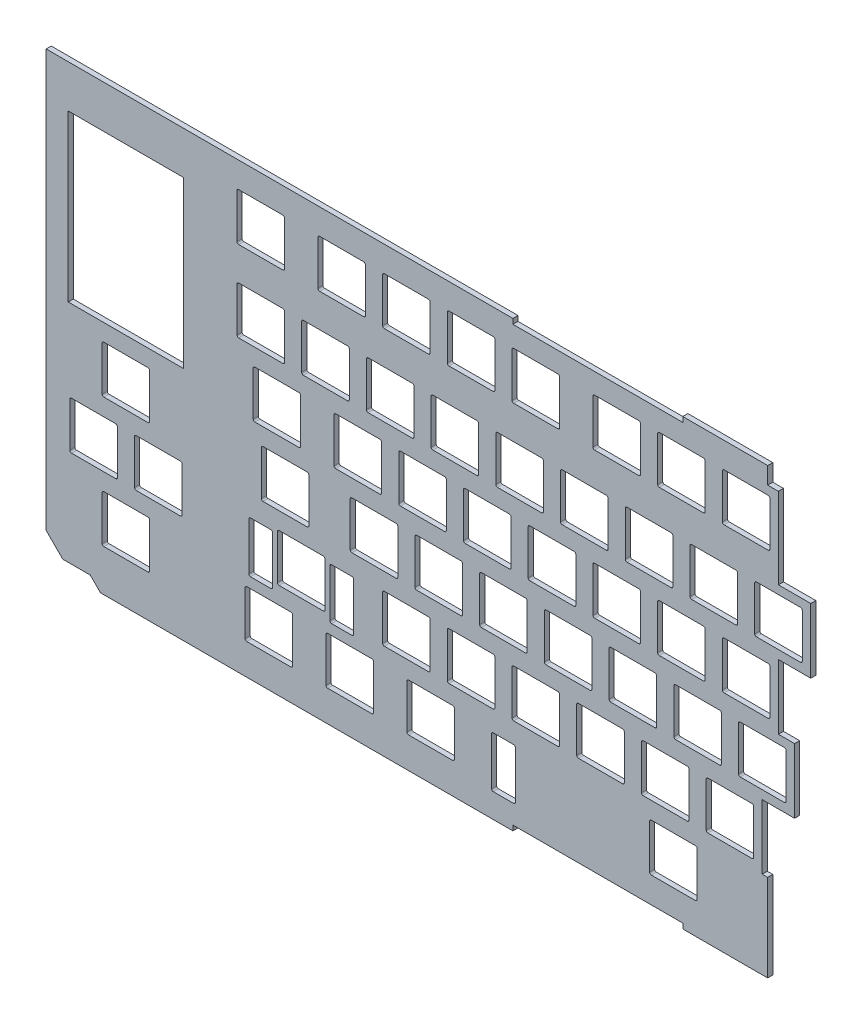
SolidWorks part; units mm, degrees
ref_plane "Přední rovina" through (0, 0, 0) normal (0, 0, 1) x (1, 0, 0)
ref_plane "Horní rovina" through (0, 0, 0) normal (0, 1, 0) x (1, 0, 0)
ref_plane "Pravá rovina" through (0, 0, 0) normal (1, 0, 0) x (0, 0, -1)
sketch "Model" plane through (0, 0, 0) normal (0, 0, 1) x (1, 0, 0)
  line L0 (53.8256, -2.525) -> (66.8256, -2.525)
  line L1 (53.8256, -16.525) -> (66.8256, -16.525)
  line L2 (53.3256, -3.025) -> (53.3256, -16.025)
  line L3 (67.3256, -3.025) -> (67.3256, -16.025)
  line L4 (77.6381, -2.525) -> (90.6381, -2.525)
  line L5 (77.6381, -16.525) -> (90.6381, -16.525)
  line L6 (77.1381, -3.025) -> (77.1381, -16.025)
  line L7 (91.1381, -3.025) -> (91.1381, -16.025)
  line L8 (96.6881, -2.525) -> (109.6881, -2.525)
  line L9 (96.6881, -16.525) -> (109.6881, -16.525)
  line L10 (96.1881, -3.025) -> (96.1881, -16.025)
  line L11 (110.1881, -3.025) -> (110.1881, -16.025)
  line L12 (115.7381, -2.525) -> (128.7381, -2.525)
  line L13 (115.7381, -16.525) -> (128.7381, -16.525)
  line L14 (115.2381, -3.025) -> (115.2381, -16.025)
  line L15 (129.2381, -3.025) -> (129.2381, -16.025)
  line L16 (134.7881, -2.525) -> (147.7881, -2.525)
  line L17 (134.7881, -16.525) -> (147.7881, -16.525)
  line L18 (134.2881, -3.025) -> (134.2881, -16.025)
  line L19 (148.2881, -3.025) -> (148.2881, -16.025)
  line L20 (158.6006, -2.525) -> (171.6006, -2.525)
  line L21 (158.6006, -16.525) -> (171.6006, -16.525)
  line L22 (158.1006, -3.025) -> (158.1006, -16.025)
  line L23 (172.1006, -3.025) -> (172.1006, -16.025)
  line L24 (177.6506, -2.525) -> (190.6506, -2.525)
  line L25 (177.6506, -16.525) -> (190.6506, -16.525)
  line L26 (177.1506, -3.025) -> (177.1506, -16.025)
  line L27 (191.1506, -3.025) -> (191.1506, -16.025)
  line L28 (196.7006, -2.525) -> (209.7006, -2.525)
  line L29 (196.7006, -16.525) -> (209.7006, -16.525)
  line L30 (196.2006, -3.025) -> (196.2006, -16.025)
  line L31 (210.2006, -3.025) -> (210.2006, -16.025)
  line L32 (215.7506, -2.525) -> (228.7506, -2.525)
  line L33 (215.7506, -16.525) -> (228.7506, -16.525)
  line L34 (215.2506, -3.025) -> (215.2506, -16.025)
  line L35 (229.2506, -3.025) -> (229.2506, -16.025)
  line L36 (239.5631, -2.525) -> (252.5631, -2.525)
  line L37 (239.5631, -16.525) -> (252.5631, -16.525)
  line L38 (239.0631, -3.025) -> (239.0631, -16.025)
  line L39 (253.0631, -3.025) -> (253.0631, -16.025)
  line L40 (258.6131, -2.525) -> (271.6131, -2.525)
  line L41 (258.6131, -16.525) -> (271.6131, -16.525)
  line L42 (258.1131, -3.025) -> (258.1131, -16.025)
  line L43 (272.1131, -3.025) -> (272.1131, -16.025)
  line L44 (277.6631, -2.525) -> (290.6631, -2.525)
  line L45 (277.6631, -16.525) -> (290.6631, -16.525)
  line L46 (277.1631, -3.025) -> (277.1631, -16.025)
  line L47 (291.1631, -3.025) -> (291.1631, -16.025)
  line L48 (296.7131, -2.525) -> (309.7131, -2.525)
  line L49 (296.7131, -16.525) -> (309.7131, -16.525)
  line L50 (296.2131, -3.025) -> (296.2131, -16.025)
  line L51 (310.2131, -3.025) -> (310.2131, -16.025)
  line L52 (320.5256, -2.525) -> (333.5256, -2.525)
  line L53 (320.5256, -16.525) -> (333.5256, -16.525)
  line L54 (320.0256, -3.025) -> (320.0256, -16.025)
  line L55 (334.0256, -3.025) -> (334.0256, -16.025)
  line L56 (344.3381, -2.525) -> (357.3381, -2.525)
  line L57 (344.3381, -16.525) -> (357.3381, -16.525)
  line L58 (343.8381, -3.025) -> (343.8381, -16.025)
  line L59 (357.8381, -3.025) -> (357.8381, -16.025)
  line L60 (363.3881, -2.525) -> (376.3881, -2.525)
  line L61 (363.3881, -16.525) -> (376.3881, -16.525)
  line L62 (362.8881, -3.025) -> (362.8881, -16.025)
  line L63 (376.8881, -3.025) -> (376.8881, -16.025)
  line L64 (382.4381, -2.525) -> (395.4381, -2.525)
  line L65 (382.4381, -16.525) -> (395.4381, -16.525)
  line L66 (381.9381, -3.025) -> (381.9381, -16.025)
  line L67 (395.9381, -3.025) -> (395.9381, -16.025)
  line L68 (401.4881, -2.525) -> (414.4881, -2.525)
  line L69 (401.4881, -16.525) -> (414.4881, -16.525)
  line L70 (400.9881, -3.025) -> (400.9881, -16.025)
  line L71 (414.9881, -3.025) -> (414.9881, -16.025)
  line L72 (53.8256, -26.3375) -> (66.8256, -26.3375)
  line L73 (53.8256, -40.3375) -> (66.8256, -40.3375)
  line L74 (53.3256, -26.8375) -> (53.3256, -39.8375)
  line L75 (67.3256, -26.8375) -> (67.3256, -39.8375)
  line L76 (72.8756, -26.3375) -> (85.8756, -26.3375)
  line L77 (72.8756, -40.3375) -> (85.8756, -40.3375)
  line L78 (72.3756, -26.8375) -> (72.3756, -39.8375)
  line L79 (86.3756, -26.8375) -> (86.3756, -39.8375)
  line L80 (91.9256, -26.3375) -> (104.9256, -26.3375)
  line L81 (91.9256, -40.3375) -> (104.9256, -40.3375)
  line L82 (91.4256, -26.8375) -> (91.4256, -39.8375)
  line L83 (105.4256, -26.8375) -> (105.4256, -39.8375)
  line L84 (110.9756, -26.3375) -> (123.9756, -26.3375)
  line L85 (110.9756, -40.3375) -> (123.9756, -40.3375)
  line L86 (110.4756, -26.8375) -> (110.4756, -39.8375)
  line L87 (124.4756, -26.8375) -> (124.4756, -39.8375)
  line L88 (130.0256, -26.3375) -> (143.0256, -26.3375)
  line L89 (130.0256, -40.3375) -> (143.0256, -40.3375)
  line L90 (129.5256, -26.8375) -> (129.5256, -39.8375)
  line L91 (143.5256, -26.8375) -> (143.5256, -39.8375)
  line L92 (149.0756, -26.3375) -> (162.0756, -26.3375)
  line L93 (149.0756, -40.3375) -> (162.0756, -40.3375)
  line L94 (148.5756, -26.8375) -> (148.5756, -39.8375)
  line L95 (162.5756, -26.8375) -> (162.5756, -39.8375)
  line L96 (168.1256, -26.3375) -> (181.1256, -26.3375)
  line L97 (168.1256, -40.3375) -> (181.1256, -40.3375)
  line L98 (167.6256, -26.8375) -> (167.6256, -39.8375)
  line L99 (181.6256, -26.8375) -> (181.6256, -39.8375)
  line L100 (187.1756, -26.3375) -> (200.1756, -26.3375)
  line L101 (187.1756, -40.3375) -> (200.1756, -40.3375)
  line L102 (186.6756, -26.8375) -> (186.6756, -39.8375)
  line L103 (200.6756, -26.8375) -> (200.6756, -39.8375)
  line L104 (206.2256, -26.3375) -> (219.2256, -26.3375)
  line L105 (206.2256, -40.3375) -> (219.2256, -40.3375)
  line L106 (205.7256, -26.8375) -> (205.7256, -39.8375)
  line L107 (219.7256, -26.8375) -> (219.7256, -39.8375)
  line L108 (225.2756, -26.3375) -> (238.2756, -26.3375)
  line L109 (225.2756, -40.3375) -> (238.2756, -40.3375)
  line L110 (224.7756, -26.8375) -> (224.7756, -39.8375)
  line L111 (238.7756, -26.8375) -> (238.7756, -39.8375)
  line L112 (244.3256, -26.3375) -> (257.3256, -26.3375)
  line L113 (244.3256, -40.3375) -> (257.3256, -40.3375)
  line L114 (243.8256, -26.8375) -> (243.8256, -39.8375)
  line L115 (257.8256, -26.8375) -> (257.8256, -39.8375)
  line L116 (263.3756, -26.3375) -> (276.3756, -26.3375)
  line L117 (263.3756, -40.3375) -> (276.3756, -40.3375)
  line L118 (262.8756, -26.8375) -> (262.8756, -39.8375)
  line L119 (276.8756, -26.8375) -> (276.8756, -39.8375)
  line L120 (282.4256, -26.3375) -> (295.4256, -26.3375)
  line L121 (282.4256, -40.3375) -> (295.4256, -40.3375)
  line L122 (281.9256, -26.8375) -> (281.9256, -39.8375)
  line L123 (295.9256, -26.8375) -> (295.9256, -39.8375)
  line L124 (311.0006, -26.3375) -> (324.0006, -26.3375)
  line L125 (311.0006, -40.3375) -> (324.0006, -40.3375)
  line L126 (310.5006, -26.8375) -> (310.5006, -39.8375)
  line L127 (324.5006, -26.8375) -> (324.5006, -39.8375)
  line L128 (302.5626, -27.3375) -> (308.5626, -27.3375)
  line L129 (302.5626, -42.3375) -> (308.5626, -42.3375)
  line L130 (302.0626, -27.8375) -> (302.0626, -41.8375)
  line L131 (309.0626, -27.8375) -> (309.0626, -41.8375)
  line L132 (326.4386, -27.3375) -> (332.4386, -27.3375)
  line L133 (326.4386, -42.3375) -> (332.4386, -42.3375)
  line L134 (325.9386, -27.8375) -> (325.9386, -41.8375)
  line L135 (332.9386, -27.8375) -> (332.9386, -41.8375)
  line L136 (342.7513, -26.3375) -> (355.7513, -26.3375)
  line L137 (342.7513, -40.3375) -> (355.7513, -40.3375)
  line L138 (342.2513, -26.8375) -> (342.2513, -39.8375)
  line L139 (356.2513, -26.8375) -> (356.2513, -39.8375)
  line L140 (361.8013, -26.3375) -> (374.8013, -26.3375)
  line L141 (361.8013, -40.3375) -> (374.8013, -40.3375)
  line L142 (361.3013, -26.8375) -> (361.3013, -39.8375)
  line L143 (375.3013, -26.8375) -> (375.3013, -39.8375)
  line L144 (380.8513, -26.3375) -> (393.8513, -26.3375)
  line L145 (380.8513, -40.3375) -> (393.8513, -40.3375)
  line L146 (380.3513, -26.8375) -> (380.3513, -39.8375)
  line L147 (394.3513, -26.8375) -> (394.3513, -39.8375)
  line L148 (399.9013, -26.3375) -> (412.9013, -26.3375)
  line L149 (399.9013, -40.3375) -> (412.9013, -40.3375)
  line L150 (399.4013, -26.8375) -> (399.4013, -39.8375)
  line L151 (413.4013, -26.8375) -> (413.4013, -39.8375)
  line L152 (58.5881, -45.3875) -> (71.5881, -45.3875)
  line L153 (58.5881, -59.3875) -> (71.5881, -59.3875)
  line L154 (58.0881, -45.8875) -> (58.0881, -58.8875)
  line L155 (72.0881, -45.8875) -> (72.0881, -58.8875)
  line L156 (82.4006, -45.3875) -> (95.4006, -45.3875)
  line L157 (82.4006, -59.3875) -> (95.4006, -59.3875)
  line L158 (81.9006, -45.8875) -> (81.9006, -58.8875)
  line L159 (95.9006, -45.8875) -> (95.9006, -58.8875)
  line L160 (101.4506, -45.3875) -> (114.4506, -45.3875)
  line L161 (101.4506, -59.3875) -> (114.4506, -59.3875)
  line L162 (100.9506, -45.8875) -> (100.9506, -58.8875)
  line L163 (114.9506, -45.8875) -> (114.9506, -58.8875)
  line L164 (120.5006, -45.3875) -> (133.5006, -45.3875)
  line L165 (120.5006, -59.3875) -> (133.5006, -59.3875)
  line L166 (120.0006, -45.8875) -> (120.0006, -58.8875)
  line L167 (134.0006, -45.8875) -> (134.0006, -58.8875)
  line L168 (139.5506, -45.3875) -> (152.5506, -45.3875)
  line L169 (139.5506, -59.3875) -> (152.5506, -59.3875)
  line L170 (139.0506, -45.8875) -> (139.0506, -58.8875)
  line L171 (153.0506, -45.8875) -> (153.0506, -58.8875)
  line L172 (158.6006, -45.3875) -> (171.6006, -45.3875)
  line L173 (158.6006, -59.3875) -> (171.6006, -59.3875)
  line L174 (158.1006, -45.8875) -> (158.1006, -58.8875)
  line L175 (172.1006, -45.8875) -> (172.1006, -58.8875)
  line L176 (177.6506, -45.3875) -> (190.6506, -45.3875)
  line L177 (177.6506, -59.3875) -> (190.6506, -59.3875)
  line L178 (177.1506, -45.8875) -> (177.1506, -58.8875)
  line L179 (191.1506, -45.8875) -> (191.1506, -58.8875)
  line L180 (196.7006, -45.3875) -> (209.7006, -45.3875)
  line L181 (196.7006, -59.3875) -> (209.7006, -59.3875)
  line L182 (196.2006, -45.8875) -> (196.2006, -58.8875)
  line L183 (210.2006, -45.8875) -> (210.2006, -58.8875)
  line L184 (215.7506, -45.3875) -> (228.7506, -45.3875)
  line L185 (215.7506, -59.3875) -> (228.7506, -59.3875)
  line L186 (215.2506, -45.8875) -> (215.2506, -58.8875)
  line L187 (229.2506, -45.8875) -> (229.2506, -58.8875)
  line L188 (234.8006, -45.3875) -> (247.8006, -45.3875)
  line L189 (234.8006, -59.3875) -> (247.8006, -59.3875)
  line L190 (234.3006, -45.8875) -> (234.3006, -58.8875)
  line L191 (248.3006, -45.8875) -> (248.3006, -58.8875)
  line L192 (253.8506, -45.3875) -> (266.8506, -45.3875)
  line L193 (253.8506, -59.3875) -> (266.8506, -59.3875)
  line L194 (253.3506, -45.8875) -> (253.3506, -58.8875)
  line L195 (267.3506, -45.8875) -> (267.3506, -58.8875)
  line L196 (272.9006, -45.3875) -> (285.9006, -45.3875)
  line L197 (272.9006, -59.3875) -> (285.9006, -59.3875)
  line L198 (272.4006, -45.8875) -> (272.4006, -58.8875)
  line L199 (286.4006, -45.8875) -> (286.4006, -58.8875)
  line L200 (291.9506, -45.3875) -> (304.9506, -45.3875)
  line L201 (291.9506, -59.3875) -> (304.9506, -59.3875)
  line L202 (291.4506, -45.8875) -> (291.4506, -58.8875)
  line L203 (305.4506, -45.8875) -> (305.4506, -58.8875)
  line L204 (315.7631, -45.3875) -> (328.7631, -45.3875)
  line L205 (315.7631, -59.3875) -> (328.7631, -59.3875)
  line L206 (315.2631, -45.8875) -> (315.2631, -58.8875)
  line L207 (329.2631, -45.8875) -> (329.2631, -58.8875)
  line L208 (342.7513, -45.3875) -> (355.7513, -45.3875)
  line L209 (342.7513, -59.3875) -> (355.7513, -59.3875)
  line L210 (342.2513, -45.8875) -> (342.2513, -58.8875)
  line L211 (356.2513, -45.8875) -> (356.2513, -58.8875)
  line L212 (361.8013, -45.3875) -> (374.8013, -45.3875)
  line L213 (361.8013, -59.3875) -> (374.8013, -59.3875)
  line L214 (361.3013, -45.8875) -> (361.3013, -58.8875)
  line L215 (375.3013, -45.8875) -> (375.3013, -58.8875)
  line L216 (380.8513, -45.3875) -> (393.8513, -45.3875)
  line L217 (380.8513, -59.3875) -> (393.8513, -59.3875)
  line L218 (380.3513, -45.8875) -> (380.3513, -58.8875)
  line L219 (394.3513, -45.8875) -> (394.3513, -58.8875)
  line L220 (413.4013, -55.4125) -> (413.4013, -68.4125)
  line L221 (399.4013, -55.4125) -> (399.4013, -68.4125)
  line L222 (412.9013, -54.9125) -> (399.9013, -54.9125)
  line L223 (412.9013, -68.9125) -> (399.9013, -68.9125)
  line L224 (412.4013, -46.9745) -> (412.4013, -52.9745)
  line L225 (397.4013, -46.9745) -> (397.4013, -52.9745)
  line L226 (411.9013, -46.4745) -> (397.9013, -46.4745)
  line L227 (411.9013, -53.4745) -> (397.9013, -53.4745)
  line L228 (412.4013, -70.8505) -> (412.4013, -76.8505)
  line L229 (397.4013, -70.8505) -> (397.4013, -76.8505)
  line L230 (411.9013, -70.3505) -> (397.9013, -70.3505)
  line L231 (411.9013, -77.3505) -> (397.9013, -77.3505)
  line L232 (14.1369, -61.2619) -> (27.1369, -61.2619)
  line L233 (14.1369, -75.2619) -> (27.1369, -75.2619)
  line L234 (13.6369, -61.7619) -> (13.6369, -74.7619)
  line L235 (27.6369, -61.7619) -> (27.6369, -74.7619)
  line L236 (60.9694, -64.4375) -> (73.9694, -64.4375)
  line L237 (60.9694, -78.4375) -> (73.9694, -78.4375)
  line L238 (60.4694, -64.9375) -> (60.4694, -77.9375)
  line L239 (74.4694, -64.9375) -> (74.4694, -77.9375)
  line L240 (87.1631, -64.4375) -> (100.1631, -64.4375)
  line L241 (87.1631, -78.4375) -> (100.1631, -78.4375)
  line L242 (86.6631, -64.9375) -> (86.6631, -77.9375)
  line L243 (100.6631, -64.9375) -> (100.6631, -77.9375)
  line L244 (106.2131, -64.4375) -> (119.2131, -64.4375)
  line L245 (106.2131, -78.4375) -> (119.2131, -78.4375)
  line L246 (105.7131, -64.9375) -> (105.7131, -77.9375)
  line L247 (119.7131, -64.9375) -> (119.7131, -77.9375)
  line L248 (125.2631, -64.4375) -> (138.2631, -64.4375)
  line L249 (125.2631, -78.4375) -> (138.2631, -78.4375)
  line L250 (124.7631, -64.9375) -> (124.7631, -77.9375)
  line L251 (138.7631, -64.9375) -> (138.7631, -77.9375)
  line L252 (144.3131, -64.4375) -> (157.3131, -64.4375)
  line L253 (144.3131, -78.4375) -> (157.3131, -78.4375)
  line L254 (143.8131, -64.9375) -> (143.8131, -77.9375)
  line L255 (157.8131, -64.9375) -> (157.8131, -77.9375)
  line L256 (163.3631, -64.4375) -> (176.3631, -64.4375)
  line L257 (163.3631, -78.4375) -> (176.3631, -78.4375)
  line L258 (162.8631, -64.9375) -> (162.8631, -77.9375)
  line L259 (176.8631, -64.9375) -> (176.8631, -77.9375)
  line L260 (182.4131, -64.4375) -> (195.4131, -64.4375)
  line L261 (182.4131, -78.4375) -> (195.4131, -78.4375)
  line L262 (181.9131, -64.9375) -> (181.9131, -77.9375)
  line L263 (195.9131, -64.9375) -> (195.9131, -77.9375)
  line L264 (201.4631, -64.4375) -> (214.4631, -64.4375)
  line L265 (201.4631, -78.4375) -> (214.4631, -78.4375)
  line L266 (200.9631, -64.9375) -> (200.9631, -77.9375)
  line L267 (214.9631, -64.9375) -> (214.9631, -77.9375)
  line L268 (220.5131, -64.4375) -> (233.5131, -64.4375)
  line L269 (220.5131, -78.4375) -> (233.5131, -78.4375)
  line L270 (220.0131, -64.9375) -> (220.0131, -77.9375)
  line L271 (234.0131, -64.9375) -> (234.0131, -77.9375)
  line L272 (239.5631, -64.4375) -> (252.5631, -64.4375)
  line L273 (239.5631, -78.4375) -> (252.5631, -78.4375)
  line L274 (239.0631, -64.9375) -> (239.0631, -77.9375)
  line L275 (253.0631, -64.9375) -> (253.0631, -77.9375)
  line L276 (258.6131, -64.4375) -> (271.6131, -64.4375)
  line L277 (258.6131, -78.4375) -> (271.6131, -78.4375)
  line L278 (258.1131, -64.9375) -> (258.1131, -77.9375)
  line L279 (272.1131, -64.9375) -> (272.1131, -77.9375)
  line L280 (277.6631, -64.4375) -> (290.6631, -64.4375)
  line L281 (277.6631, -78.4375) -> (290.6631, -78.4375)
  line L282 (277.1631, -64.9375) -> (277.1631, -77.9375)
  line L283 (291.1631, -64.9375) -> (291.1631, -77.9375)
  line L284 (308.6194, -64.4375) -> (321.6194, -64.4375)
  line L285 (308.6194, -78.4375) -> (321.6194, -78.4375)
  line L286 (308.1194, -64.9375) -> (308.1194, -77.9375)
  line L287 (322.1194, -64.9375) -> (322.1194, -77.9375)
  line L288 (300.1814, -65.4375) -> (306.1814, -65.4375)
  line L289 (300.1814, -80.4375) -> (306.1814, -80.4375)
  line L290 (299.6814, -65.9375) -> (299.6814, -79.9375)
  line L291 (306.6814, -65.9375) -> (306.6814, -79.9375)
  line L292 (324.0574, -65.4375) -> (330.0574, -65.4375)
  line L293 (324.0574, -80.4375) -> (330.0574, -80.4375)
  line L294 (323.5574, -65.9375) -> (323.5574, -79.9375)
  line L295 (330.5574, -65.9375) -> (330.5574, -79.9375)
  line L296 (342.7513, -64.4375) -> (355.7513, -64.4375)
  line L297 (342.7513, -78.4375) -> (355.7513, -78.4375)
  line L298 (342.2513, -64.9375) -> (342.2513, -77.9375)
  line L299 (356.2513, -64.9375) -> (356.2513, -77.9375)
  line L300 (361.8013, -64.4375) -> (374.8013, -64.4375)
  line L301 (361.8013, -78.4375) -> (374.8013, -78.4375)
  line L302 (361.3013, -64.9375) -> (361.3013, -77.9375)
  line L303 (375.3013, -64.9375) -> (375.3013, -77.9375)
  line L304 (380.8513, -64.4375) -> (393.8513, -64.4375)
  line L305 (380.8513, -78.4375) -> (393.8513, -78.4375)
  line L306 (380.3513, -64.9375) -> (380.3513, -77.9375)
  line L307 (394.3513, -64.9375) -> (394.3513, -77.9375)
  line L308 (4.6119, -80.3119) -> (17.6119, -80.3119)
  line L309 (4.6119, -94.3119) -> (17.6119, -94.3119)
  line L310 (4.1119, -80.8119) -> (4.1119, -93.8119)
  line L311 (18.1119, -80.8119) -> (18.1119, -93.8119)
  line L312 (23.6619, -80.3119) -> (36.6619, -80.3119)
  line L313 (23.6619, -94.3119) -> (36.6619, -94.3119)
  line L314 (23.1619, -80.8119) -> (23.1619, -93.8119)
  line L315 (37.1619, -80.8119) -> (37.1619, -93.8119)
  line L316 (65.7319, -83.4875) -> (78.7319, -83.4875)
  line L317 (65.7319, -97.4875) -> (78.7319, -97.4875)
  line L318 (65.2319, -83.9875) -> (65.2319, -96.9875)
  line L319 (79.2319, -83.9875) -> (79.2319, -96.9875)
  line L320 (57.2939, -84.4875) -> (63.2939, -84.4875)
  line L321 (57.2939, -99.4875) -> (63.2939, -99.4875)
  line L322 (56.7939, -84.9875) -> (56.7939, -98.9875)
  line L323 (63.7939, -84.9875) -> (63.7939, -98.9875)
  line L324 (81.1699, -84.4875) -> (87.1699, -84.4875)
  line L325 (81.1699, -99.4875) -> (87.1699, -99.4875)
  line L326 (80.6699, -84.9875) -> (80.6699, -98.9875)
  line L327 (87.6699, -84.9875) -> (87.6699, -98.9875)
  line L328 (96.6881, -83.4875) -> (109.6881, -83.4875)
  line L329 (96.6881, -97.4875) -> (109.6881, -97.4875)
  line L330 (96.1881, -83.9875) -> (96.1881, -96.9875)
  line L331 (110.1881, -83.9875) -> (110.1881, -96.9875)
  line L332 (115.7381, -83.4875) -> (128.7381, -83.4875)
  line L333 (115.7381, -97.4875) -> (128.7381, -97.4875)
  line L334 (115.2381, -83.9875) -> (115.2381, -96.9875)
  line L335 (129.2381, -83.9875) -> (129.2381, -96.9875)
  line L336 (134.7881, -83.4875) -> (147.7881, -83.4875)
  line L337 (134.7881, -97.4875) -> (147.7881, -97.4875)
  line L338 (134.2881, -83.9875) -> (134.2881, -96.9875)
  line L339 (148.2881, -83.9875) -> (148.2881, -96.9875)
  line L340 (153.8381, -83.4875) -> (166.8381, -83.4875)
  line L341 (153.8381, -97.4875) -> (166.8381, -97.4875)
  line L342 (153.3381, -83.9875) -> (153.3381, -96.9875)
  line L343 (167.3381, -83.9875) -> (167.3381, -96.9875)
  line L344 (172.8881, -83.4875) -> (185.8881, -83.4875)
  line L345 (172.8881, -97.4875) -> (185.8881, -97.4875)
  line L346 (172.3881, -83.9875) -> (172.3881, -96.9875)
  line L347 (186.3881, -83.9875) -> (186.3881, -96.9875)
  line L348 (191.9381, -83.4875) -> (204.9381, -83.4875)
  line L349 (191.9381, -97.4875) -> (204.9381, -97.4875)
  line L350 (191.4381, -83.9875) -> (191.4381, -96.9875)
  line L351 (205.4381, -83.9875) -> (205.4381, -96.9875)
  line L352 (210.9881, -83.4875) -> (223.9881, -83.4875)
  line L353 (210.9881, -97.4875) -> (223.9881, -97.4875)
  line L354 (210.4881, -83.9875) -> (210.4881, -96.9875)
  line L355 (224.4881, -83.9875) -> (224.4881, -96.9875)
  line L356 (230.0381, -83.4875) -> (243.0381, -83.4875)
  line L357 (230.0381, -97.4875) -> (243.0381, -97.4875)
  line L358 (229.5381, -83.9875) -> (229.5381, -96.9875)
  line L359 (243.5381, -83.9875) -> (243.5381, -96.9875)
  line L360 (249.0881, -83.4875) -> (262.0881, -83.4875)
  line L361 (249.0881, -97.4875) -> (262.0881, -97.4875)
  line L362 (248.5881, -83.9875) -> (248.5881, -96.9875)
  line L363 (262.5881, -83.9875) -> (262.5881, -96.9875)
  line L364 (268.1381, -83.4875) -> (281.1381, -83.4875)
  line L365 (268.1381, -97.4875) -> (281.1381, -97.4875)
  line L366 (267.6381, -83.9875) -> (267.6381, -96.9875)
  line L367 (281.6381, -83.9875) -> (281.6381, -96.9875)
  line L368 (294.3319, -83.4875) -> (307.3319, -83.4875)
  line L369 (294.3319, -97.4875) -> (307.3319, -97.4875)
  line L370 (293.8319, -83.9875) -> (293.8319, -96.9875)
  line L371 (307.8319, -83.9875) -> (307.8319, -96.9875)
  line L372 (342.7513, -83.4875) -> (355.7513, -83.4875)
  line L373 (342.7513, -97.4875) -> (355.7513, -97.4875)
  line L374 (342.2513, -83.9875) -> (342.2513, -96.9875)
  line L375 (356.2513, -83.9875) -> (356.2513, -96.9875)
  line L376 (361.8013, -83.4875) -> (374.8013, -83.4875)
  line L377 (361.8013, -97.4875) -> (374.8013, -97.4875)
  line L378 (361.3013, -83.9875) -> (361.3013, -96.9875)
  line L379 (375.3013, -83.9875) -> (375.3013, -96.9875)
  line L380 (380.8513, -83.4875) -> (393.8513, -83.4875)
  line L381 (380.8513, -97.4875) -> (393.8513, -97.4875)
  line L382 (380.3513, -83.9875) -> (380.3513, -96.9875)
  line L383 (394.3513, -83.9875) -> (394.3513, -96.9875)
  line L384 (413.4013, -93.5125) -> (413.4013, -106.5125)
  line L385 (399.4013, -93.5125) -> (399.4013, -106.5125)
  line L386 (412.9013, -93.0125) -> (399.9013, -93.0125)
  line L387 (412.9013, -107.0125) -> (399.9013, -107.0125)
  line L396 (322.1125, -85.0744) -> (335.1125, -85.0744)
  line L397 (322.1125, -99.0744) -> (335.1125, -99.0744)
  line L398 (321.6125, -85.5744) -> (321.6125, -98.5744)
  line L399 (335.6125, -85.5744) -> (335.6125, -98.5744)
  line L400 (14.1369, -99.3619) -> (27.1369, -99.3619)
  line L401 (14.1369, -113.3619) -> (27.1369, -113.3619)
  line L402 (13.6369, -99.8619) -> (13.6369, -112.8619)
  line L403 (27.6369, -99.8619) -> (27.6369, -112.8619)
  line L404 (56.2069, -102.5375) -> (69.2069, -102.5375)
  line L405 (56.2069, -116.5375) -> (69.2069, -116.5375)
  line L406 (55.7069, -103.0375) -> (55.7069, -116.0375)
  line L407 (69.7069, -103.0375) -> (69.7069, -116.0375)
  line L408 (80.0194, -102.5375) -> (93.0194, -102.5375)
  line L409 (80.0194, -116.5375) -> (93.0194, -116.5375)
  line L410 (79.5194, -103.0375) -> (79.5194, -116.0375)
  line L411 (93.5194, -103.0375) -> (93.5194, -116.0375)
  line L412 (103.8319, -102.5375) -> (116.8319, -102.5375)
  line L413 (103.8319, -116.5375) -> (116.8319, -116.5375)
  line L414 (103.3319, -103.0375) -> (103.3319, -116.0375)
  line L415 (117.3319, -103.0375) -> (117.3319, -116.0375)
  line L416 (175.2694, -102.5375) -> (188.2694, -102.5375)
  line L417 (175.2694, -116.5375) -> (188.2694, -116.5375)
  line L418 (174.7694, -103.0375) -> (174.7694, -116.0375)
  line L419 (188.7694, -103.0375) -> (188.7694, -116.0375)
  line L420 (128.7694, -103.5375) -> (134.7694, -103.5375)
  line L421 (128.7694, -118.5375) -> (134.7694, -118.5375)
  line L422 (128.2694, -104.0375) -> (128.2694, -118.0375)
  line L423 (135.2694, -104.0375) -> (135.2694, -118.0375)
  line L424 (228.7694, -103.5375) -> (234.7694, -103.5375)
  line L425 (228.7694, -118.5375) -> (234.7694, -118.5375)
  line L426 (228.2694, -104.0375) -> (228.2694, -118.0375)
  line L427 (235.2694, -104.0375) -> (235.2694, -118.0375)
  line L428 (244.3256, -102.5375) -> (257.3256, -102.5375)
  line L429 (244.3256, -116.5375) -> (257.3256, -116.5375)
  line L430 (243.8256, -103.0375) -> (243.8256, -116.0375)
  line L431 (257.8256, -103.0375) -> (257.8256, -116.0375)
  line L432 (263.3756, -102.5375) -> (276.3756, -102.5375)
  line L433 (263.3756, -116.5375) -> (276.3756, -116.5375)
  line L434 (262.8756, -103.0375) -> (262.8756, -116.0375)
  line L435 (276.8756, -103.0375) -> (276.8756, -116.0375)
  line L436 (282.4256, -102.5375) -> (295.4256, -102.5375)
  line L437 (282.4256, -116.5375) -> (295.4256, -116.5375)
  line L438 (281.9256, -103.0375) -> (281.9256, -116.0375)
  line L439 (295.9256, -103.0375) -> (295.9256, -116.0375)
  line L440 (361.8013, -102.5375) -> (374.8013, -102.5375)
  line L441 (361.8013, -116.5375) -> (374.8013, -116.5375)
  line L442 (361.3013, -103.0375) -> (361.3013, -116.0375)
  line L443 (375.3013, -103.0375) -> (375.3013, -116.0375)
  line L444 (380.8513, -102.5375) -> (393.8513, -102.5375)
  line L445 (380.8513, -116.5375) -> (393.8513, -116.5375)
  line L446 (380.3513, -103.0375) -> (380.3513, -116.0375)
  line L447 (394.3513, -103.0375) -> (394.3513, -116.0375)
  line L448 (303.0625, -104.1244) -> (316.0625, -104.1244)
  line L449 (303.0625, -118.1244) -> (316.0625, -118.1244)
  line L450 (302.5625, -104.6244) -> (302.5625, -117.6244)
  line L451 (316.5625, -104.6244) -> (316.5625, -117.6244)
  line L452 (322.1125, -104.1244) -> (335.1125, -104.1244)
  line L453 (322.1125, -118.1244) -> (335.1125, -118.1244)
  line L454 (321.6125, -104.6244) -> (321.6125, -117.6244)
  line L455 (335.6125, -104.6244) -> (335.6125, -117.6244)
  line L456 (341.1625, -104.1244) -> (354.1625, -104.1244)
  line L457 (341.1625, -118.1244) -> (354.1625, -118.1244)
  line L458 (340.6625, -104.6244) -> (340.6625, -117.6244)
  line L459 (354.6625, -104.6244) -> (354.6625, -117.6244)
  line L460 (1.5869, -120.6494) -> (417.5131, -120.6494)
  line L461 (1.5869, 0) -> (417.5131, 0)
  line L462 (1.5869, -120.6494) -> (1.5869, 0)
  line L463 (417.5131, -120.6494) -> (417.5131, 0)
  arc A0 (53.8256, -2.525) -> (53.3256, -3.025) centre (53.8256, -3.025) ccw
  arc A1 (67.3256, -3.025) -> (66.8256, -2.525) centre (66.8256, -3.025) ccw
  arc A2 (53.3256, -16.025) -> (53.8256, -16.525) centre (53.8256, -16.025) ccw
  arc A3 (66.8256, -16.525) -> (67.3256, -16.025) centre (66.8256, -16.025) ccw
  arc A4 (77.6381, -2.525) -> (77.1381, -3.025) centre (77.6381, -3.025) ccw
  arc A5 (91.1381, -3.025) -> (90.6381, -2.525) centre (90.6381, -3.025) ccw
  arc A6 (77.1381, -16.025) -> (77.6381, -16.525) centre (77.6381, -16.025) ccw
  arc A7 (90.6381, -16.525) -> (91.1381, -16.025) centre (90.6381, -16.025) ccw
  arc A8 (96.6881, -2.525) -> (96.1881, -3.025) centre (96.6881, -3.025) ccw
  arc A9 (110.1881, -3.025) -> (109.6881, -2.525) centre (109.6881, -3.025) ccw
  arc A10 (96.1881, -16.025) -> (96.6881, -16.525) centre (96.6881, -16.025) ccw
  arc A11 (109.6881, -16.525) -> (110.1881, -16.025) centre (109.6881, -16.025) ccw
  arc A12 (115.7381, -2.525) -> (115.2381, -3.025) centre (115.7381, -3.025) ccw
  arc A13 (129.2381, -3.025) -> (128.7381, -2.525) centre (128.7381, -3.025) ccw
  arc A14 (115.2381, -16.025) -> (115.7381, -16.525) centre (115.7381, -16.025) ccw
  arc A15 (128.7381, -16.525) -> (129.2381, -16.025) centre (128.7381, -16.025) ccw
  arc A16 (134.7881, -2.525) -> (134.2881, -3.025) centre (134.7881, -3.025) ccw
  arc A17 (148.2881, -3.025) -> (147.7881, -2.525) centre (147.7881, -3.025) ccw
  arc A18 (134.2881, -16.025) -> (134.7881, -16.525) centre (134.7881, -16.025) ccw
  arc A19 (147.7881, -16.525) -> (148.2881, -16.025) centre (147.7881, -16.025) ccw
  arc A20 (158.6006, -2.525) -> (158.1006, -3.025) centre (158.6006, -3.025) ccw
  arc A21 (172.1006, -3.025) -> (171.6006, -2.525) centre (171.6006, -3.025) ccw
  arc A22 (158.1006, -16.025) -> (158.6006, -16.525) centre (158.6006, -16.025) ccw
  arc A23 (171.6006, -16.525) -> (172.1006, -16.025) centre (171.6006, -16.025) ccw
  arc A24 (177.6506, -2.525) -> (177.1506, -3.025) centre (177.6506, -3.025) ccw
  arc A25 (191.1506, -3.025) -> (190.6506, -2.525) centre (190.6506, -3.025) ccw
  arc A26 (177.1506, -16.025) -> (177.6506, -16.525) centre (177.6506, -16.025) ccw
  arc A27 (190.6506, -16.525) -> (191.1506, -16.025) centre (190.6506, -16.025) ccw
  arc A28 (196.7006, -2.525) -> (196.2006, -3.025) centre (196.7006, -3.025) ccw
  arc A29 (210.2006, -3.025) -> (209.7006, -2.525) centre (209.7006, -3.025) ccw
  arc A30 (196.2006, -16.025) -> (196.7006, -16.525) centre (196.7006, -16.025) ccw
  arc A31 (209.7006, -16.525) -> (210.2006, -16.025) centre (209.7006, -16.025) ccw
  arc A32 (215.7506, -2.525) -> (215.2506, -3.025) centre (215.7506, -3.025) ccw
  arc A33 (229.2506, -3.025) -> (228.7506, -2.525) centre (228.7506, -3.025) ccw
  arc A34 (215.2506, -16.025) -> (215.7506, -16.525) centre (215.7506, -16.025) ccw
  arc A35 (228.7506, -16.525) -> (229.2506, -16.025) centre (228.7506, -16.025) ccw
  arc A36 (239.5631, -2.525) -> (239.0631, -3.025) centre (239.5631, -3.025) ccw
  arc A37 (253.0631, -3.025) -> (252.5631, -2.525) centre (252.5631, -3.025) ccw
  arc A38 (239.0631, -16.025) -> (239.5631, -16.525) centre (239.5631, -16.025) ccw
  arc A39 (252.5631, -16.525) -> (253.0631, -16.025) centre (252.5631, -16.025) ccw
  arc A40 (258.6131, -2.525) -> (258.1131, -3.025) centre (258.6131, -3.025) ccw
  arc A41 (272.1131, -3.025) -> (271.6131, -2.525) centre (271.6131, -3.025) ccw
  arc A42 (258.1131, -16.025) -> (258.6131, -16.525) centre (258.6131, -16.025) ccw
  arc A43 (271.6131, -16.525) -> (272.1131, -16.025) centre (271.6131, -16.025) ccw
  arc A44 (277.6631, -2.525) -> (277.1631, -3.025) centre (277.6631, -3.025) ccw
  arc A45 (291.1631, -3.025) -> (290.6631, -2.525) centre (290.6631, -3.025) ccw
  arc A46 (277.1631, -16.025) -> (277.6631, -16.525) centre (277.6631, -16.025) ccw
  arc A47 (290.6631, -16.525) -> (291.1631, -16.025) centre (290.6631, -16.025) ccw
  arc A48 (296.7131, -2.525) -> (296.2131, -3.025) centre (296.7131, -3.025) ccw
  arc A49 (310.2131, -3.025) -> (309.7131, -2.525) centre (309.7131, -3.025) ccw
  arc A50 (296.2131, -16.025) -> (296.7131, -16.525) centre (296.7131, -16.025) ccw
  arc A51 (309.7131, -16.525) -> (310.2131, -16.025) centre (309.7131, -16.025) ccw
  arc A52 (320.5256, -2.525) -> (320.0256, -3.025) centre (320.5256, -3.025) ccw
  arc A53 (334.0256, -3.025) -> (333.5256, -2.525) centre (333.5256, -3.025) ccw
  arc A54 (320.0256, -16.025) -> (320.5256, -16.525) centre (320.5256, -16.025) ccw
  arc A55 (333.5256, -16.525) -> (334.0256, -16.025) centre (333.5256, -16.025) ccw
  arc A56 (344.3381, -2.525) -> (343.8381, -3.025) centre (344.3381, -3.025) ccw
  arc A57 (357.8381, -3.025) -> (357.3381, -2.525) centre (357.3381, -3.025) ccw
  arc A58 (343.8381, -16.025) -> (344.3381, -16.525) centre (344.3381, -16.025) ccw
  arc A59 (357.3381, -16.525) -> (357.8381, -16.025) centre (357.3381, -16.025) ccw
  arc A60 (363.3881, -2.525) -> (362.8881, -3.025) centre (363.3881, -3.025) ccw
  arc A61 (376.8881, -3.025) -> (376.3881, -2.525) centre (376.3881, -3.025) ccw
  arc A62 (362.8881, -16.025) -> (363.3881, -16.525) centre (363.3881, -16.025) ccw
  arc A63 (376.3881, -16.525) -> (376.8881, -16.025) centre (376.3881, -16.025) ccw
  arc A64 (382.4381, -2.525) -> (381.9381, -3.025) centre (382.4381, -3.025) ccw
  arc A65 (395.9381, -3.025) -> (395.4381, -2.525) centre (395.4381, -3.025) ccw
  arc A66 (381.9381, -16.025) -> (382.4381, -16.525) centre (382.4381, -16.025) ccw
  arc A67 (395.4381, -16.525) -> (395.9381, -16.025) centre (395.4381, -16.025) ccw
  arc A68 (401.4881, -2.525) -> (400.9881, -3.025) centre (401.4881, -3.025) ccw
  arc A69 (414.9881, -3.025) -> (414.4881, -2.525) centre (414.4881, -3.025) ccw
  arc A70 (400.9881, -16.025) -> (401.4881, -16.525) centre (401.4881, -16.025) ccw
  arc A71 (414.4881, -16.525) -> (414.9881, -16.025) centre (414.4881, -16.025) ccw
  arc A72 (53.8256, -26.3375) -> (53.3256, -26.8375) centre (53.8256, -26.8375) ccw
  arc A73 (67.3256, -26.8375) -> (66.8256, -26.3375) centre (66.8256, -26.8375) ccw
  arc A74 (53.3256, -39.8375) -> (53.8256, -40.3375) centre (53.8256, -39.8375) ccw
  arc A75 (66.8256, -40.3375) -> (67.3256, -39.8375) centre (66.8256, -39.8375) ccw
  arc A76 (72.8756, -26.3375) -> (72.3756, -26.8375) centre (72.8756, -26.8375) ccw
  arc A77 (86.3756, -26.8375) -> (85.8756, -26.3375) centre (85.8756, -26.8375) ccw
  arc A78 (72.3756, -39.8375) -> (72.8756, -40.3375) centre (72.8756, -39.8375) ccw
  arc A79 (85.8756, -40.3375) -> (86.3756, -39.8375) centre (85.8756, -39.8375) ccw
  arc A80 (91.9256, -26.3375) -> (91.4256, -26.8375) centre (91.9256, -26.8375) ccw
  arc A81 (105.4256, -26.8375) -> (104.9256, -26.3375) centre (104.9256, -26.8375) ccw
  arc A82 (91.4256, -39.8375) -> (91.9256, -40.3375) centre (91.9256, -39.8375) ccw
  arc A83 (104.9256, -40.3375) -> (105.4256, -39.8375) centre (104.9256, -39.8375) ccw
  arc A84 (110.9756, -26.3375) -> (110.4756, -26.8375) centre (110.9756, -26.8375) ccw
  arc A85 (124.4756, -26.8375) -> (123.9756, -26.3375) centre (123.9756, -26.8375) ccw
  arc A86 (110.4756, -39.8375) -> (110.9756, -40.3375) centre (110.9756, -39.8375) ccw
  arc A87 (123.9756, -40.3375) -> (124.4756, -39.8375) centre (123.9756, -39.8375) ccw
  arc A88 (130.0256, -26.3375) -> (129.5256, -26.8375) centre (130.0256, -26.8375) ccw
  arc A89 (143.5256, -26.8375) -> (143.0256, -26.3375) centre (143.0256, -26.8375) ccw
  arc A90 (129.5256, -39.8375) -> (130.0256, -40.3375) centre (130.0256, -39.8375) ccw
  arc A91 (143.0256, -40.3375) -> (143.5256, -39.8375) centre (143.0256, -39.8375) ccw
  arc A92 (149.0756, -26.3375) -> (148.5756, -26.8375) centre (149.0756, -26.8375) ccw
  arc A93 (162.5756, -26.8375) -> (162.0756, -26.3375) centre (162.0756, -26.8375) ccw
  arc A94 (148.5756, -39.8375) -> (149.0756, -40.3375) centre (149.0756, -39.8375) ccw
  arc A95 (162.0756, -40.3375) -> (162.5756, -39.8375) centre (162.0756, -39.8375) ccw
  arc A96 (168.1256, -26.3375) -> (167.6256, -26.8375) centre (168.1256, -26.8375) ccw
  arc A97 (181.6256, -26.8375) -> (181.1256, -26.3375) centre (181.1256, -26.8375) ccw
  arc A98 (167.6256, -39.8375) -> (168.1256, -40.3375) centre (168.1256, -39.8375) ccw
  arc A99 (181.1256, -40.3375) -> (181.6256, -39.8375) centre (181.1256, -39.8375) ccw
  arc A100 (187.1756, -26.3375) -> (186.6756, -26.8375) centre (187.1756, -26.8375) ccw
  arc A101 (200.6756, -26.8375) -> (200.1756, -26.3375) centre (200.1756, -26.8375) ccw
  arc A102 (186.6756, -39.8375) -> (187.1756, -40.3375) centre (187.1756, -39.8375) ccw
  arc A103 (200.1756, -40.3375) -> (200.6756, -39.8375) centre (200.1756, -39.8375) ccw
  arc A104 (206.2256, -26.3375) -> (205.7256, -26.8375) centre (206.2256, -26.8375) ccw
  arc A105 (219.7256, -26.8375) -> (219.2256, -26.3375) centre (219.2256, -26.8375) ccw
  arc A106 (205.7256, -39.8375) -> (206.2256, -40.3375) centre (206.2256, -39.8375) ccw
  arc A107 (219.2256, -40.3375) -> (219.7256, -39.8375) centre (219.2256, -39.8375) ccw
  arc A108 (225.2756, -26.3375) -> (224.7756, -26.8375) centre (225.2756, -26.8375) ccw
  arc A109 (238.7756, -26.8375) -> (238.2756, -26.3375) centre (238.2756, -26.8375) ccw
  arc A110 (224.7756, -39.8375) -> (225.2756, -40.3375) centre (225.2756, -39.8375) ccw
  arc A111 (238.2756, -40.3375) -> (238.7756, -39.8375) centre (238.2756, -39.8375) ccw
  arc A112 (244.3256, -26.3375) -> (243.8256, -26.8375) centre (244.3256, -26.8375) ccw
  arc A113 (257.8256, -26.8375) -> (257.3256, -26.3375) centre (257.3256, -26.8375) ccw
  arc A114 (243.8256, -39.8375) -> (244.3256, -40.3375) centre (244.3256, -39.8375) ccw
  arc A115 (257.3256, -40.3375) -> (257.8256, -39.8375) centre (257.3256, -39.8375) ccw
  arc A116 (263.3756, -26.3375) -> (262.8756, -26.8375) centre (263.3756, -26.8375) ccw
  arc A117 (276.8756, -26.8375) -> (276.3756, -26.3375) centre (276.3756, -26.8375) ccw
  arc A118 (262.8756, -39.8375) -> (263.3756, -40.3375) centre (263.3756, -39.8375) ccw
  arc A119 (276.3756, -40.3375) -> (276.8756, -39.8375) centre (276.3756, -39.8375) ccw
  arc A120 (282.4256, -26.3375) -> (281.9256, -26.8375) centre (282.4256, -26.8375) ccw
  arc A121 (295.9256, -26.8375) -> (295.4256, -26.3375) centre (295.4256, -26.8375) ccw
  arc A122 (281.9256, -39.8375) -> (282.4256, -40.3375) centre (282.4256, -39.8375) ccw
  arc A123 (295.4256, -40.3375) -> (295.9256, -39.8375) centre (295.4256, -39.8375) ccw
  arc A124 (311.0006, -26.3375) -> (310.5006, -26.8375) centre (311.0006, -26.8375) ccw
  arc A125 (324.5006, -26.8375) -> (324.0006, -26.3375) centre (324.0006, -26.8375) ccw
  arc A126 (310.5006, -39.8375) -> (311.0006, -40.3375) centre (311.0006, -39.8375) ccw
  arc A127 (324.0006, -40.3375) -> (324.5006, -39.8375) centre (324.0006, -39.8375) ccw
  arc A128 (302.5626, -27.3375) -> (302.0626, -27.8375) centre (302.5626, -27.8375) ccw
  arc A129 (309.0626, -27.8375) -> (308.5626, -27.3375) centre (308.5626, -27.8375) ccw
  arc A130 (302.0626, -41.8375) -> (302.5626, -42.3375) centre (302.5626, -41.8375) ccw
  arc A131 (308.5626, -42.3375) -> (309.0626, -41.8375) centre (308.5626, -41.8375) ccw
  arc A132 (326.4386, -27.3375) -> (325.9386, -27.8375) centre (326.4386, -27.8375) ccw
  arc A133 (332.9386, -27.8375) -> (332.4386, -27.3375) centre (332.4386, -27.8375) ccw
  arc A134 (325.9386, -41.8375) -> (326.4386, -42.3375) centre (326.4386, -41.8375) ccw
  arc A135 (332.4386, -42.3375) -> (332.9386, -41.8375) centre (332.4386, -41.8375) ccw
  arc A136 (342.7513, -26.3375) -> (342.2513, -26.8375) centre (342.7513, -26.8375) ccw
  arc A137 (356.2513, -26.8375) -> (355.7513, -26.3375) centre (355.7513, -26.8375) ccw
  arc A138 (342.2513, -39.8375) -> (342.7513, -40.3375) centre (342.7513, -39.8375) ccw
  arc A139 (355.7513, -40.3375) -> (356.2513, -39.8375) centre (355.7513, -39.8375) ccw
  arc A140 (361.8013, -26.3375) -> (361.3013, -26.8375) centre (361.8013, -26.8375) ccw
  arc A141 (375.3013, -26.8375) -> (374.8013, -26.3375) centre (374.8013, -26.8375) ccw
  arc A142 (361.3013, -39.8375) -> (361.8013, -40.3375) centre (361.8013, -39.8375) ccw
  arc A143 (374.8013, -40.3375) -> (375.3013, -39.8375) centre (374.8013, -39.8375) ccw
  arc A144 (380.8513, -26.3375) -> (380.3513, -26.8375) centre (380.8513, -26.8375) ccw
  arc A145 (394.3513, -26.8375) -> (393.8513, -26.3375) centre (393.8513, -26.8375) ccw
  arc A146 (380.3513, -39.8375) -> (380.8513, -40.3375) centre (380.8513, -39.8375) ccw
  arc A147 (393.8513, -40.3375) -> (394.3513, -39.8375) centre (393.8513, -39.8375) ccw
  arc A148 (399.9013, -26.3375) -> (399.4013, -26.8375) centre (399.9013, -26.8375) ccw
  arc A149 (413.4013, -26.8375) -> (412.9013, -26.3375) centre (412.9013, -26.8375) ccw
  arc A150 (399.4013, -39.8375) -> (399.9013, -40.3375) centre (399.9013, -39.8375) ccw
  arc A151 (412.9013, -40.3375) -> (413.4013, -39.8375) centre (412.9013, -39.8375) ccw
  arc A152 (58.5881, -45.3875) -> (58.0881, -45.8875) centre (58.5881, -45.8875) ccw
  arc A153 (72.0881, -45.8875) -> (71.5881, -45.3875) centre (71.5881, -45.8875) ccw
  arc A154 (58.0881, -58.8875) -> (58.5881, -59.3875) centre (58.5881, -58.8875) ccw
  arc A155 (71.5881, -59.3875) -> (72.0881, -58.8875) centre (71.5881, -58.8875) ccw
  arc A156 (82.4006, -45.3875) -> (81.9006, -45.8875) centre (82.4006, -45.8875) ccw
  arc A157 (95.9006, -45.8875) -> (95.4006, -45.3875) centre (95.4006, -45.8875) ccw
  arc A158 (81.9006, -58.8875) -> (82.4006, -59.3875) centre (82.4006, -58.8875) ccw
  arc A159 (95.4006, -59.3875) -> (95.9006, -58.8875) centre (95.4006, -58.8875) ccw
  arc A160 (101.4506, -45.3875) -> (100.9506, -45.8875) centre (101.4506, -45.8875) ccw
  arc A161 (114.9506, -45.8875) -> (114.4506, -45.3875) centre (114.4506, -45.8875) ccw
  arc A162 (100.9506, -58.8875) -> (101.4506, -59.3875) centre (101.4506, -58.8875) ccw
  arc A163 (114.4506, -59.3875) -> (114.9506, -58.8875) centre (114.4506, -58.8875) ccw
  arc A164 (120.5006, -45.3875) -> (120.0006, -45.8875) centre (120.5006, -45.8875) ccw
  arc A165 (134.0006, -45.8875) -> (133.5006, -45.3875) centre (133.5006, -45.8875) ccw
  arc A166 (120.0006, -58.8875) -> (120.5006, -59.3875) centre (120.5006, -58.8875) ccw
  arc A167 (133.5006, -59.3875) -> (134.0006, -58.8875) centre (133.5006, -58.8875) ccw
  arc A168 (139.5506, -45.3875) -> (139.0506, -45.8875) centre (139.5506, -45.8875) ccw
  arc A169 (153.0506, -45.8875) -> (152.5506, -45.3875) centre (152.5506, -45.8875) ccw
  arc A170 (139.0506, -58.8875) -> (139.5506, -59.3875) centre (139.5506, -58.8875) ccw
  arc A171 (152.5506, -59.3875) -> (153.0506, -58.8875) centre (152.5506, -58.8875) ccw
  arc A172 (158.6006, -45.3875) -> (158.1006, -45.8875) centre (158.6006, -45.8875) ccw
  arc A173 (172.1006, -45.8875) -> (171.6006, -45.3875) centre (171.6006, -45.8875) ccw
  arc A174 (158.1006, -58.8875) -> (158.6006, -59.3875) centre (158.6006, -58.8875) ccw
  arc A175 (171.6006, -59.3875) -> (172.1006, -58.8875) centre (171.6006, -58.8875) ccw
  arc A176 (177.6506, -45.3875) -> (177.1506, -45.8875) centre (177.6506, -45.8875) ccw
  arc A177 (191.1506, -45.8875) -> (190.6506, -45.3875) centre (190.6506, -45.8875) ccw
  arc A178 (177.1506, -58.8875) -> (177.6506, -59.3875) centre (177.6506, -58.8875) ccw
  arc A179 (190.6506, -59.3875) -> (191.1506, -58.8875) centre (190.6506, -58.8875) ccw
  arc A180 (196.7006, -45.3875) -> (196.2006, -45.8875) centre (196.7006, -45.8875) ccw
  arc A181 (210.2006, -45.8875) -> (209.7006, -45.3875) centre (209.7006, -45.8875) ccw
  arc A182 (196.2006, -58.8875) -> (196.7006, -59.3875) centre (196.7006, -58.8875) ccw
  arc A183 (209.7006, -59.3875) -> (210.2006, -58.8875) centre (209.7006, -58.8875) ccw
  arc A184 (215.7506, -45.3875) -> (215.2506, -45.8875) centre (215.7506, -45.8875) ccw
  arc A185 (229.2506, -45.8875) -> (228.7506, -45.3875) centre (228.7506, -45.8875) ccw
  arc A186 (215.2506, -58.8875) -> (215.7506, -59.3875) centre (215.7506, -58.8875) ccw
  arc A187 (228.7506, -59.3875) -> (229.2506, -58.8875) centre (228.7506, -58.8875) ccw
  arc A188 (234.8006, -45.3875) -> (234.3006, -45.8875) centre (234.8006, -45.8875) ccw
  arc A189 (248.3006, -45.8875) -> (247.8006, -45.3875) centre (247.8006, -45.8875) ccw
  arc A190 (234.3006, -58.8875) -> (234.8006, -59.3875) centre (234.8006, -58.8875) ccw
  arc A191 (247.8006, -59.3875) -> (248.3006, -58.8875) centre (247.8006, -58.8875) ccw
  arc A192 (253.8506, -45.3875) -> (253.3506, -45.8875) centre (253.8506, -45.8875) ccw
  arc A193 (267.3506, -45.8875) -> (266.8506, -45.3875) centre (266.8506, -45.8875) ccw
  arc A194 (253.3506, -58.8875) -> (253.8506, -59.3875) centre (253.8506, -58.8875) ccw
  arc A195 (266.8506, -59.3875) -> (267.3506, -58.8875) centre (266.8506, -58.8875) ccw
  arc A196 (272.9006, -45.3875) -> (272.4006, -45.8875) centre (272.9006, -45.8875) ccw
  arc A197 (286.4006, -45.8875) -> (285.9006, -45.3875) centre (285.9006, -45.8875) ccw
  arc A198 (272.4006, -58.8875) -> (272.9006, -59.3875) centre (272.9006, -58.8875) ccw
  arc A199 (285.9006, -59.3875) -> (286.4006, -58.8875) centre (285.9006, -58.8875) ccw
  arc A200 (291.9506, -45.3875) -> (291.4506, -45.8875) centre (291.9506, -45.8875) ccw
  arc A201 (305.4506, -45.8875) -> (304.9506, -45.3875) centre (304.9506, -45.8875) ccw
  arc A202 (291.4506, -58.8875) -> (291.9506, -59.3875) centre (291.9506, -58.8875) ccw
  arc A203 (304.9506, -59.3875) -> (305.4506, -58.8875) centre (304.9506, -58.8875) ccw
  arc A204 (315.7631, -45.3875) -> (315.2631, -45.8875) centre (315.7631, -45.8875) ccw
  arc A205 (329.2631, -45.8875) -> (328.7631, -45.3875) centre (328.7631, -45.8875) ccw
  arc A206 (315.2631, -58.8875) -> (315.7631, -59.3875) centre (315.7631, -58.8875) ccw
  arc A207 (328.7631, -59.3875) -> (329.2631, -58.8875) centre (328.7631, -58.8875) ccw
  arc A208 (342.7513, -45.3875) -> (342.2513, -45.8875) centre (342.7513, -45.8875) ccw
  arc A209 (356.2513, -45.8875) -> (355.7513, -45.3875) centre (355.7513, -45.8875) ccw
  arc A210 (342.2513, -58.8875) -> (342.7513, -59.3875) centre (342.7513, -58.8875) ccw
  arc A211 (355.7513, -59.3875) -> (356.2513, -58.8875) centre (355.7513, -58.8875) ccw
  arc A212 (361.8013, -45.3875) -> (361.3013, -45.8875) centre (361.8013, -45.8875) ccw
  arc A213 (375.3013, -45.8875) -> (374.8013, -45.3875) centre (374.8013, -45.8875) ccw
  arc A214 (361.3013, -58.8875) -> (361.8013, -59.3875) centre (361.8013, -58.8875) ccw
  arc A215 (374.8013, -59.3875) -> (375.3013, -58.8875) centre (374.8013, -58.8875) ccw
  arc A216 (380.8513, -45.3875) -> (380.3513, -45.8875) centre (380.8513, -45.8875) ccw
  arc A217 (394.3513, -45.8875) -> (393.8513, -45.3875) centre (393.8513, -45.8875) ccw
  arc A218 (380.3513, -58.8875) -> (380.8513, -59.3875) centre (380.8513, -58.8875) ccw
  arc A219 (393.8513, -59.3875) -> (394.3513, -58.8875) centre (393.8513, -58.8875) ccw
  arc A220 (413.4013, -55.4125) -> (412.9013, -54.9125) centre (412.9013, -55.4125) ccw
  arc A221 (412.9013, -68.9125) -> (413.4013, -68.4125) centre (412.9013, -68.4125) ccw
  arc A222 (399.9013, -54.9125) -> (399.4013, -55.4125) centre (399.9013, -55.4125) ccw
  arc A223 (399.4013, -68.4125) -> (399.9013, -68.9125) centre (399.9013, -68.4125) ccw
  arc A224 (412.4013, -46.9745) -> (411.9013, -46.4745) centre (411.9013, -46.9745) ccw
  arc A225 (411.9013, -53.4745) -> (412.4013, -52.9745) centre (411.9013, -52.9745) ccw
  arc A226 (397.9013, -46.4745) -> (397.4013, -46.9745) centre (397.9013, -46.9745) ccw
  arc A227 (397.4013, -52.9745) -> (397.9013, -53.4745) centre (397.9013, -52.9745) ccw
  arc A228 (412.4013, -70.8505) -> (411.9013, -70.3505) centre (411.9013, -70.8505) ccw
  arc A229 (411.9013, -77.3505) -> (412.4013, -76.8505) centre (411.9013, -76.8505) ccw
  arc A230 (397.9013, -70.3505) -> (397.4013, -70.8505) centre (397.9013, -70.8505) ccw
  arc A231 (397.4013, -76.8505) -> (397.9013, -77.3505) centre (397.9013, -76.8505) ccw
  arc A232 (14.1369, -61.2619) -> (13.6369, -61.7619) centre (14.1369, -61.7619) ccw
  arc A233 (27.6369, -61.7619) -> (27.1369, -61.2619) centre (27.1369, -61.7619) ccw
  arc A234 (13.6369, -74.7619) -> (14.1369, -75.2619) centre (14.1369, -74.7619) ccw
  arc A235 (27.1369, -75.2619) -> (27.6369, -74.7619) centre (27.1369, -74.7619) ccw
  arc A236 (60.9694, -64.4375) -> (60.4694, -64.9375) centre (60.9694, -64.9375) ccw
  arc A237 (74.4694, -64.9375) -> (73.9694, -64.4375) centre (73.9694, -64.9375) ccw
  arc A238 (60.4694, -77.9375) -> (60.9694, -78.4375) centre (60.9694, -77.9375) ccw
  arc A239 (73.9694, -78.4375) -> (74.4694, -77.9375) centre (73.9694, -77.9375) ccw
  arc A240 (87.1631, -64.4375) -> (86.6631, -64.9375) centre (87.1631, -64.9375) ccw
  arc A241 (100.6631, -64.9375) -> (100.1631, -64.4375) centre (100.1631, -64.9375) ccw
  arc A242 (86.6631, -77.9375) -> (87.1631, -78.4375) centre (87.1631, -77.9375) ccw
  arc A243 (100.1631, -78.4375) -> (100.6631, -77.9375) centre (100.1631, -77.9375) ccw
  arc A244 (106.2131, -64.4375) -> (105.7131, -64.9375) centre (106.2131, -64.9375) ccw
  arc A245 (119.7131, -64.9375) -> (119.2131, -64.4375) centre (119.2131, -64.9375) ccw
  arc A246 (105.7131, -77.9375) -> (106.2131, -78.4375) centre (106.2131, -77.9375) ccw
  arc A247 (119.2131, -78.4375) -> (119.7131, -77.9375) centre (119.2131, -77.9375) ccw
  arc A248 (125.2631, -64.4375) -> (124.7631, -64.9375) centre (125.2631, -64.9375) ccw
  arc A249 (138.7631, -64.9375) -> (138.2631, -64.4375) centre (138.2631, -64.9375) ccw
  arc A250 (124.7631, -77.9375) -> (125.2631, -78.4375) centre (125.2631, -77.9375) ccw
  arc A251 (138.2631, -78.4375) -> (138.7631, -77.9375) centre (138.2631, -77.9375) ccw
  arc A252 (144.3131, -64.4375) -> (143.8131, -64.9375) centre (144.3131, -64.9375) ccw
  arc A253 (157.8131, -64.9375) -> (157.3131, -64.4375) centre (157.3131, -64.9375) ccw
  arc A254 (143.8131, -77.9375) -> (144.3131, -78.4375) centre (144.3131, -77.9375) ccw
  arc A255 (157.3131, -78.4375) -> (157.8131, -77.9375) centre (157.3131, -77.9375) ccw
  arc A256 (163.3631, -64.4375) -> (162.8631, -64.9375) centre (163.3631, -64.9375) ccw
  arc A257 (176.8631, -64.9375) -> (176.3631, -64.4375) centre (176.3631, -64.9375) ccw
  arc A258 (162.8631, -77.9375) -> (163.3631, -78.4375) centre (163.3631, -77.9375) ccw
  arc A259 (176.3631, -78.4375) -> (176.8631, -77.9375) centre (176.3631, -77.9375) ccw
  arc A260 (182.4131, -64.4375) -> (181.9131, -64.9375) centre (182.4131, -64.9375) ccw
  arc A261 (195.9131, -64.9375) -> (195.4131, -64.4375) centre (195.4131, -64.9375) ccw
  arc A262 (181.9131, -77.9375) -> (182.4131, -78.4375) centre (182.4131, -77.9375) ccw
  arc A263 (195.4131, -78.4375) -> (195.9131, -77.9375) centre (195.4131, -77.9375) ccw
  arc A264 (201.4631, -64.4375) -> (200.9631, -64.9375) centre (201.4631, -64.9375) ccw
  arc A265 (214.9631, -64.9375) -> (214.4631, -64.4375) centre (214.4631, -64.9375) ccw
  arc A266 (200.9631, -77.9375) -> (201.4631, -78.4375) centre (201.4631, -77.9375) ccw
  arc A267 (214.4631, -78.4375) -> (214.9631, -77.9375) centre (214.4631, -77.9375) ccw
  arc A268 (220.5131, -64.4375) -> (220.0131, -64.9375) centre (220.5131, -64.9375) ccw
  arc A269 (234.0131, -64.9375) -> (233.5131, -64.4375) centre (233.5131, -64.9375) ccw
  arc A270 (220.0131, -77.9375) -> (220.5131, -78.4375) centre (220.5131, -77.9375) ccw
  arc A271 (233.5131, -78.4375) -> (234.0131, -77.9375) centre (233.5131, -77.9375) ccw
  arc A272 (239.5631, -64.4375) -> (239.0631, -64.9375) centre (239.5631, -64.9375) ccw
  arc A273 (253.0631, -64.9375) -> (252.5631, -64.4375) centre (252.5631, -64.9375) ccw
  arc A274 (239.0631, -77.9375) -> (239.5631, -78.4375) centre (239.5631, -77.9375) ccw
  arc A275 (252.5631, -78.4375) -> (253.0631, -77.9375) centre (252.5631, -77.9375) ccw
  arc A276 (258.6131, -64.4375) -> (258.1131, -64.9375) centre (258.6131, -64.9375) ccw
  arc A277 (272.1131, -64.9375) -> (271.6131, -64.4375) centre (271.6131, -64.9375) ccw
  arc A278 (258.1131, -77.9375) -> (258.6131, -78.4375) centre (258.6131, -77.9375) ccw
  arc A279 (271.6131, -78.4375) -> (272.1131, -77.9375) centre (271.6131, -77.9375) ccw
  arc A280 (277.6631, -64.4375) -> (277.1631, -64.9375) centre (277.6631, -64.9375) ccw
  arc A281 (291.1631, -64.9375) -> (290.6631, -64.4375) centre (290.6631, -64.9375) ccw
  arc A282 (277.1631, -77.9375) -> (277.6631, -78.4375) centre (277.6631, -77.9375) ccw
  arc A283 (290.6631, -78.4375) -> (291.1631, -77.9375) centre (290.6631, -77.9375) ccw
  arc A284 (308.6194, -64.4375) -> (308.1194, -64.9375) centre (308.6194, -64.9375) ccw
  arc A285 (322.1194, -64.9375) -> (321.6194, -64.4375) centre (321.6194, -64.9375) ccw
  arc A286 (308.1194, -77.9375) -> (308.6194, -78.4375) centre (308.6194, -77.9375) ccw
  arc A287 (321.6194, -78.4375) -> (322.1194, -77.9375) centre (321.6194, -77.9375) ccw
  arc A288 (300.1814, -65.4375) -> (299.6814, -65.9375) centre (300.1814, -65.9375) ccw
  arc A289 (306.6814, -65.9375) -> (306.1814, -65.4375) centre (306.1814, -65.9375) ccw
  arc A290 (299.6814, -79.9375) -> (300.1814, -80.4375) centre (300.1814, -79.9375) ccw
  arc A291 (306.1814, -80.4375) -> (306.6814, -79.9375) centre (306.1814, -79.9375) ccw
  arc A292 (324.0574, -65.4375) -> (323.5574, -65.9375) centre (324.0574, -65.9375) ccw
  arc A293 (330.5574, -65.9375) -> (330.0574, -65.4375) centre (330.0574, -65.9375) ccw
  arc A294 (323.5574, -79.9375) -> (324.0574, -80.4375) centre (324.0574, -79.9375) ccw
  arc A295 (330.0574, -80.4375) -> (330.5574, -79.9375) centre (330.0574, -79.9375) ccw
  arc A296 (342.7513, -64.4375) -> (342.2513, -64.9375) centre (342.7513, -64.9375) ccw
  arc A297 (356.2513, -64.9375) -> (355.7513, -64.4375) centre (355.7513, -64.9375) ccw
  arc A298 (342.2513, -77.9375) -> (342.7513, -78.4375) centre (342.7513, -77.9375) ccw
  arc A299 (355.7513, -78.4375) -> (356.2513, -77.9375) centre (355.7513, -77.9375) ccw
  arc A300 (361.8013, -64.4375) -> (361.3013, -64.9375) centre (361.8013, -64.9375) ccw
  arc A301 (375.3013, -64.9375) -> (374.8013, -64.4375) centre (374.8013, -64.9375) ccw
  arc A302 (361.3013, -77.9375) -> (361.8013, -78.4375) centre (361.8013, -77.9375) ccw
  arc A303 (374.8013, -78.4375) -> (375.3013, -77.9375) centre (374.8013, -77.9375) ccw
  arc A304 (380.8513, -64.4375) -> (380.3513, -64.9375) centre (380.8513, -64.9375) ccw
  arc A305 (394.3513, -64.9375) -> (393.8513, -64.4375) centre (393.8513, -64.9375) ccw
  arc A306 (380.3513, -77.9375) -> (380.8513, -78.4375) centre (380.8513, -77.9375) ccw
  arc A307 (393.8513, -78.4375) -> (394.3513, -77.9375) centre (393.8513, -77.9375) ccw
  arc A308 (4.6119, -80.3119) -> (4.1119, -80.8119) centre (4.6119, -80.8119) ccw
  arc A309 (18.1119, -80.8119) -> (17.6119, -80.3119) centre (17.6119, -80.8119) ccw
  arc A310 (4.1119, -93.8119) -> (4.6119, -94.3119) centre (4.6119, -93.8119) ccw
  arc A311 (17.6119, -94.3119) -> (18.1119, -93.8119) centre (17.6119, -93.8119) ccw
  arc A312 (23.6619, -80.3119) -> (23.1619, -80.8119) centre (23.6619, -80.8119) ccw
  arc A313 (37.1619, -80.8119) -> (36.6619, -80.3119) centre (36.6619, -80.8119) ccw
  arc A314 (23.1619, -93.8119) -> (23.6619, -94.3119) centre (23.6619, -93.8119) ccw
  arc A315 (36.6619, -94.3119) -> (37.1619, -93.8119) centre (36.6619, -93.8119) ccw
  arc A316 (65.7319, -83.4875) -> (65.2319, -83.9875) centre (65.7319, -83.9875) ccw
  arc A317 (79.2319, -83.9875) -> (78.7319, -83.4875) centre (78.7319, -83.9875) ccw
  arc A318 (65.2319, -96.9875) -> (65.7319, -97.4875) centre (65.7319, -96.9875) ccw
  arc A319 (78.7319, -97.4875) -> (79.2319, -96.9875) centre (78.7319, -96.9875) ccw
  arc A320 (57.2939, -84.4875) -> (56.7939, -84.9875) centre (57.2939, -84.9875) ccw
  arc A321 (63.7939, -84.9875) -> (63.2939, -84.4875) centre (63.2939, -84.9875) ccw
  arc A322 (56.7939, -98.9875) -> (57.2939, -99.4875) centre (57.2939, -98.9875) ccw
  arc A323 (63.2939, -99.4875) -> (63.7939, -98.9875) centre (63.2939, -98.9875) ccw
  arc A324 (81.1699, -84.4875) -> (80.6699, -84.9875) centre (81.1699, -84.9875) ccw
  arc A325 (87.6699, -84.9875) -> (87.1699, -84.4875) centre (87.1699, -84.9875) ccw
  arc A326 (80.6699, -98.9875) -> (81.1699, -99.4875) centre (81.1699, -98.9875) ccw
  arc A327 (87.1699, -99.4875) -> (87.6699, -98.9875) centre (87.1699, -98.9875) ccw
  arc A328 (96.6881, -83.4875) -> (96.1881, -83.9875) centre (96.6881, -83.9875) ccw
  arc A329 (110.1881, -83.9875) -> (109.6881, -83.4875) centre (109.6881, -83.9875) ccw
  arc A330 (96.1881, -96.9875) -> (96.6881, -97.4875) centre (96.6881, -96.9875) ccw
  arc A331 (109.6881, -97.4875) -> (110.1881, -96.9875) centre (109.6881, -96.9875) ccw
  arc A332 (115.7381, -83.4875) -> (115.2381, -83.9875) centre (115.7381, -83.9875) ccw
  arc A333 (129.2381, -83.9875) -> (128.7381, -83.4875) centre (128.7381, -83.9875) ccw
  arc A334 (115.2381, -96.9875) -> (115.7381, -97.4875) centre (115.7381, -96.9875) ccw
  arc A335 (128.7381, -97.4875) -> (129.2381, -96.9875) centre (128.7381, -96.9875) ccw
  arc A336 (134.7881, -83.4875) -> (134.2881, -83.9875) centre (134.7881, -83.9875) ccw
  arc A337 (148.2881, -83.9875) -> (147.7881, -83.4875) centre (147.7881, -83.9875) ccw
  arc A338 (134.2881, -96.9875) -> (134.7881, -97.4875) centre (134.7881, -96.9875) ccw
  arc A339 (147.7881, -97.4875) -> (148.2881, -96.9875) centre (147.7881, -96.9875) ccw
  arc A340 (153.8381, -83.4875) -> (153.3381, -83.9875) centre (153.8381, -83.9875) ccw
  arc A341 (167.3381, -83.9875) -> (166.8381, -83.4875) centre (166.8381, -83.9875) ccw
  arc A342 (153.3381, -96.9875) -> (153.8381, -97.4875) centre (153.8381, -96.9875) ccw
  arc A343 (166.8381, -97.4875) -> (167.3381, -96.9875) centre (166.8381, -96.9875) ccw
  arc A344 (172.8881, -83.4875) -> (172.3881, -83.9875) centre (172.8881, -83.9875) ccw
  arc A345 (186.3881, -83.9875) -> (185.8881, -83.4875) centre (185.8881, -83.9875) ccw
  arc A346 (172.3881, -96.9875) -> (172.8881, -97.4875) centre (172.8881, -96.9875) ccw
  arc A347 (185.8881, -97.4875) -> (186.3881, -96.9875) centre (185.8881, -96.9875) ccw
  arc A348 (191.9381, -83.4875) -> (191.4381, -83.9875) centre (191.9381, -83.9875) ccw
  arc A349 (205.4381, -83.9875) -> (204.9381, -83.4875) centre (204.9381, -83.9875) ccw
  arc A350 (191.4381, -96.9875) -> (191.9381, -97.4875) centre (191.9381, -96.9875) ccw
  arc A351 (204.9381, -97.4875) -> (205.4381, -96.9875) centre (204.9381, -96.9875) ccw
  arc A352 (210.9881, -83.4875) -> (210.4881, -83.9875) centre (210.9881, -83.9875) ccw
  arc A353 (224.4881, -83.9875) -> (223.9881, -83.4875) centre (223.9881, -83.9875) ccw
  arc A354 (210.4881, -96.9875) -> (210.9881, -97.4875) centre (210.9881, -96.9875) ccw
  arc A355 (223.9881, -97.4875) -> (224.4881, -96.9875) centre (223.9881, -96.9875) ccw
  arc A356 (230.0381, -83.4875) -> (229.5381, -83.9875) centre (230.0381, -83.9875) ccw
  arc A357 (243.5381, -83.9875) -> (243.0381, -83.4875) centre (243.0381, -83.9875) ccw
  arc A358 (229.5381, -96.9875) -> (230.0381, -97.4875) centre (230.0381, -96.9875) ccw
  arc A359 (243.0381, -97.4875) -> (243.5381, -96.9875) centre (243.0381, -96.9875) ccw
  arc A360 (249.0881, -83.4875) -> (248.5881, -83.9875) centre (249.0881, -83.9875) ccw
  arc A361 (262.5881, -83.9875) -> (262.0881, -83.4875) centre (262.0881, -83.9875) ccw
  arc A362 (248.5881, -96.9875) -> (249.0881, -97.4875) centre (249.0881, -96.9875) ccw
  arc A363 (262.0881, -97.4875) -> (262.5881, -96.9875) centre (262.0881, -96.9875) ccw
  arc A364 (268.1381, -83.4875) -> (267.6381, -83.9875) centre (268.1381, -83.9875) ccw
  arc A365 (281.6381, -83.9875) -> (281.1381, -83.4875) centre (281.1381, -83.9875) ccw
  arc A366 (267.6381, -96.9875) -> (268.1381, -97.4875) centre (268.1381, -96.9875) ccw
  arc A367 (281.1381, -97.4875) -> (281.6381, -96.9875) centre (281.1381, -96.9875) ccw
  arc A368 (294.3319, -83.4875) -> (293.8319, -83.9875) centre (294.3319, -83.9875) ccw
  arc A369 (307.8319, -83.9875) -> (307.3319, -83.4875) centre (307.3319, -83.9875) ccw
  arc A370 (293.8319, -96.9875) -> (294.3319, -97.4875) centre (294.3319, -96.9875) ccw
  arc A371 (307.3319, -97.4875) -> (307.8319, -96.9875) centre (307.3319, -96.9875) ccw
  arc A372 (342.7513, -83.4875) -> (342.2513, -83.9875) centre (342.7513, -83.9875) ccw
  arc A373 (356.2513, -83.9875) -> (355.7513, -83.4875) centre (355.7513, -83.9875) ccw
  arc A374 (342.2513, -96.9875) -> (342.7513, -97.4875) centre (342.7513, -96.9875) ccw
  arc A375 (355.7513, -97.4875) -> (356.2513, -96.9875) centre (355.7513, -96.9875) ccw
  arc A376 (361.8013, -83.4875) -> (361.3013, -83.9875) centre (361.8013, -83.9875) ccw
  arc A377 (375.3013, -83.9875) -> (374.8013, -83.4875) centre (374.8013, -83.9875) ccw
  arc A378 (361.3013, -96.9875) -> (361.8013, -97.4875) centre (361.8013, -96.9875) ccw
  arc A379 (374.8013, -97.4875) -> (375.3013, -96.9875) centre (374.8013, -96.9875) ccw
  arc A380 (380.8513, -83.4875) -> (380.3513, -83.9875) centre (380.8513, -83.9875) ccw
  arc A381 (394.3513, -83.9875) -> (393.8513, -83.4875) centre (393.8513, -83.9875) ccw
  arc A382 (380.3513, -96.9875) -> (380.8513, -97.4875) centre (380.8513, -96.9875) ccw
  arc A383 (393.8513, -97.4875) -> (394.3513, -96.9875) centre (393.8513, -96.9875) ccw
  arc A384 (413.4013, -93.5125) -> (412.9013, -93.0125) centre (412.9013, -93.5125) ccw
  arc A385 (412.9013, -107.0125) -> (413.4013, -106.5125) centre (412.9013, -106.5125) ccw
  arc A386 (399.9013, -93.0125) -> (399.4013, -93.5125) centre (399.9013, -93.5125) ccw
  arc A387 (399.4013, -106.5125) -> (399.9013, -107.0125) centre (399.9013, -106.5125) ccw
  arc A396 (322.1125, -85.0744) -> (321.6125, -85.5744) centre (322.1125, -85.5744) ccw
  arc A397 (335.6125, -85.5744) -> (335.1125, -85.0744) centre (335.1125, -85.5744) ccw
  arc A398 (321.6125, -98.5744) -> (322.1125, -99.0744) centre (322.1125, -98.5744) ccw
  arc A399 (335.1125, -99.0744) -> (335.6125, -98.5744) centre (335.1125, -98.5744) ccw
  arc A400 (14.1369, -99.3619) -> (13.6369, -99.8619) centre (14.1369, -99.8619) ccw
  arc A401 (27.6369, -99.8619) -> (27.1369, -99.3619) centre (27.1369, -99.8619) ccw
  arc A402 (13.6369, -112.8619) -> (14.1369, -113.3619) centre (14.1369, -112.8619) ccw
  arc A403 (27.1369, -113.3619) -> (27.6369, -112.8619) centre (27.1369, -112.8619) ccw
  arc A404 (56.2069, -102.5375) -> (55.7069, -103.0375) centre (56.2069, -103.0375) ccw
  arc A405 (69.7069, -103.0375) -> (69.2069, -102.5375) centre (69.2069, -103.0375) ccw
  arc A406 (55.7069, -116.0375) -> (56.2069, -116.5375) centre (56.2069, -116.0375) ccw
  arc A407 (69.2069, -116.5375) -> (69.7069, -116.0375) centre (69.2069, -116.0375) ccw
  arc A408 (80.0194, -102.5375) -> (79.5194, -103.0375) centre (80.0194, -103.0375) ccw
  arc A409 (93.5194, -103.0375) -> (93.0194, -102.5375) centre (93.0194, -103.0375) ccw
  arc A410 (79.5194, -116.0375) -> (80.0194, -116.5375) centre (80.0194, -116.0375) ccw
  arc A411 (93.0194, -116.5375) -> (93.5194, -116.0375) centre (93.0194, -116.0375) ccw
  arc A412 (103.8319, -102.5375) -> (103.3319, -103.0375) centre (103.8319, -103.0375) ccw
  arc A413 (117.3319, -103.0375) -> (116.8319, -102.5375) centre (116.8319, -103.0375) ccw
  arc A414 (103.3319, -116.0375) -> (103.8319, -116.5375) centre (103.8319, -116.0375) ccw
  arc A415 (116.8319, -116.5375) -> (117.3319, -116.0375) centre (116.8319, -116.0375) ccw
  arc A416 (175.2694, -102.5375) -> (174.7694, -103.0375) centre (175.2694, -103.0375) ccw
  arc A417 (188.7694, -103.0375) -> (188.2694, -102.5375) centre (188.2694, -103.0375) ccw
  arc A418 (174.7694, -116.0375) -> (175.2694, -116.5375) centre (175.2694, -116.0375) ccw
  arc A419 (188.2694, -116.5375) -> (188.7694, -116.0375) centre (188.2694, -116.0375) ccw
  arc A420 (128.7694, -103.5375) -> (128.2694, -104.0375) centre (128.7694, -104.0375) ccw
  arc A421 (135.2694, -104.0375) -> (134.7694, -103.5375) centre (134.7694, -104.0375) ccw
  arc A422 (128.2694, -118.0375) -> (128.7694, -118.5375) centre (128.7694, -118.0375) ccw
  arc A423 (134.7694, -118.5375) -> (135.2694, -118.0375) centre (134.7694, -118.0375) ccw
  arc A424 (228.7694, -103.5375) -> (228.2694, -104.0375) centre (228.7694, -104.0375) ccw
  arc A425 (235.2694, -104.0375) -> (234.7694, -103.5375) centre (234.7694, -104.0375) ccw
  arc A426 (228.2694, -118.0375) -> (228.7694, -118.5375) centre (228.7694, -118.0375) ccw
  arc A427 (234.7694, -118.5375) -> (235.2694, -118.0375) centre (234.7694, -118.0375) ccw
  arc A428 (244.3256, -102.5375) -> (243.8256, -103.0375) centre (244.3256, -103.0375) ccw
  arc A429 (257.8256, -103.0375) -> (257.3256, -102.5375) centre (257.3256, -103.0375) ccw
  arc A430 (243.8256, -116.0375) -> (244.3256, -116.5375) centre (244.3256, -116.0375) ccw
  arc A431 (257.3256, -116.5375) -> (257.8256, -116.0375) centre (257.3256, -116.0375) ccw
  arc A432 (263.3756, -102.5375) -> (262.8756, -103.0375) centre (263.3756, -103.0375) ccw
  arc A433 (276.8756, -103.0375) -> (276.3756, -102.5375) centre (276.3756, -103.0375) ccw
  arc A434 (262.8756, -116.0375) -> (263.3756, -116.5375) centre (263.3756, -116.0375) ccw
  arc A435 (276.3756, -116.5375) -> (276.8756, -116.0375) centre (276.3756, -116.0375) ccw
  arc A436 (282.4256, -102.5375) -> (281.9256, -103.0375) centre (282.4256, -103.0375) ccw
  arc A437 (295.9256, -103.0375) -> (295.4256, -102.5375) centre (295.4256, -103.0375) ccw
  arc A438 (281.9256, -116.0375) -> (282.4256, -116.5375) centre (282.4256, -116.0375) ccw
  arc A439 (295.4256, -116.5375) -> (295.9256, -116.0375) centre (295.4256, -116.0375) ccw
  arc A440 (361.8013, -102.5375) -> (361.3013, -103.0375) centre (361.8013, -103.0375) ccw
  arc A441 (375.3013, -103.0375) -> (374.8013, -102.5375) centre (374.8013, -103.0375) ccw
  arc A442 (361.3013, -116.0375) -> (361.8013, -116.5375) centre (361.8013, -116.0375) ccw
  arc A443 (374.8013, -116.5375) -> (375.3013, -116.0375) centre (374.8013, -116.0375) ccw
  arc A444 (380.8513, -102.5375) -> (380.3513, -103.0375) centre (380.8513, -103.0375) ccw
  arc A445 (394.3513, -103.0375) -> (393.8513, -102.5375) centre (393.8513, -103.0375) ccw
  arc A446 (380.3513, -116.0375) -> (380.8513, -116.5375) centre (380.8513, -116.0375) ccw
  arc A447 (393.8513, -116.5375) -> (394.3513, -116.0375) centre (393.8513, -116.0375) ccw
  arc A448 (303.0625, -104.1244) -> (302.5625, -104.6244) centre (303.0625, -104.6244) ccw
  arc A449 (316.5625, -104.6244) -> (316.0625, -104.1244) centre (316.0625, -104.6244) ccw
  arc A450 (302.5625, -117.6244) -> (303.0625, -118.1244) centre (303.0625, -117.6244) ccw
  arc A451 (316.0625, -118.1244) -> (316.5625, -117.6244) centre (316.0625, -117.6244) ccw
  arc A452 (322.1125, -104.1244) -> (321.6125, -104.6244) centre (322.1125, -104.6244) ccw
  arc A453 (335.6125, -104.6244) -> (335.1125, -104.1244) centre (335.1125, -104.6244) ccw
  arc A454 (321.6125, -117.6244) -> (322.1125, -118.1244) centre (322.1125, -117.6244) ccw
  arc A455 (335.1125, -118.1244) -> (335.6125, -117.6244) centre (335.1125, -117.6244) ccw
  arc A456 (341.1625, -104.1244) -> (340.6625, -104.6244) centre (341.1625, -104.6244) ccw
  arc A457 (354.6625, -104.6244) -> (354.1625, -104.1244) centre (354.1625, -104.6244) ccw
  arc A458 (340.6625, -117.6244) -> (341.1625, -118.1244) centre (341.1625, -117.6244) ccw
  arc A459 (354.1625, -118.1244) -> (354.6625, -117.6244) centre (354.1625, -117.6244) ccw
extrude "Přidat vysunutím2" add sketch "Model" along normal blind 1.5
sketch "Skica3" plane through (0, 0, 1.5) normal (0, 0, 1) x (1, 0, 0)
  line L0 (27.1369, -61.2619) -> (14.1369, -61.2619) construction
  line L1 (3.6369, -56.2619) -> (37.6369, -56.2619)
  line L2 (3.6369, -56.2619) -> (3.6369, -7.5619)
  line L3 (3.6369, -7.5619) -> (37.6369, -7.5619)
  line L4 (37.6369, -56.2619) -> (37.6369, -7.5619)
  point P6 (20.6369, -61.2619)
  point P7 (20.6369, -56.2619)
  dimension "D1" = 5
  dimension "D2" = 48.7
  dimension "D3" = 34
extrude "Odebrat vysunutím1" cut sketch "Skica3" against normal up to next
sketch "Skica5" plane through (0, 0, 1.5) normal (0, 0, 1) x (1, 0, 0)
  line L0 (1.5869, 0) -> (417.5131, 0)
  line L1 (417.5131, 0) -> (417.5131, -120.6494)
  line L2 (417.5131, -120.6494) -> (1.5869, -120.6494)
  line L3 (1.5869, -120.6494) -> (1.5869, 0)
  line L4 (0.5869, 5) -> (134.55, 5)
  line L6 (0.5869, -125.6494) -> (0.5869, 5)
  line L8 (418.5131, -125.6494) -> (418.5131, 5)
  line L9 (134.55, 3.5) -> (184.55, 3.5)
  line L10 (184.55, 3.5) -> (184.55, 5)
  line L12 (0.5869, -125.6494) -> (134.55, -125.6494)
  line L13 (134.55, -125.6494) -> (134.55, -124.1494)
  line L14 (134.55, -124.1494) -> (184.55, -124.1494)
  line L15 (184.55, -124.1494) -> (184.55, -125.6494)
  line L17 (134.55, 5) -> (134.55, 3.5)
  line L18 (184.55, -125.6494) -> (234.55, -125.6494)
  line L19 (234.55, -125.6494) -> (234.55, -124.1494)
  line L20 (234.55, -124.1494) -> (284.55, -124.1494)
  line L21 (284.55, -124.1494) -> (284.55, -125.6494)
  line L22 (284.55, -125.6494) -> (418.5131, -125.6494)
  line L23 (184.55, 5) -> (234.55, 5)
  line L24 (234.55, 5) -> (234.55, 3.5)
  line L25 (234.55, 3.5) -> (284.55, 3.5)
  line L26 (284.55, 3.5) -> (284.55, 5)
  line L27 (284.55, 5) -> (418.5131, 5)
  point P12 (209.55, -125.6494)
  point P25 (209.55, -120.6494)
  dimension "D1" = 1
  dimension "D2" = 50
  dimension "D3" = 5
  dimension "D4" = 1
  dimension "D5" = 5
  dimension "D6" = 5
  dimension "D7" = 50
  dimension "D8" = 1.5
  dimension "D9" = 50
  dimension "D10" = 1.5
  dimension "D11" = 1.5
  dimension "D12" = 1.5
  dimension "D13" = 1.5
  dimension "D14" = 1.5
  dimension "D15" = 1.5
extrude "Přidat vysunutím3" add sketch "Skica5" against normal up to surface (1.5 mm away) up to face at (20.6369, -31.9119, 0)
sketch "Skica8" plane through (0, 0, 1.5) normal (0, 0, 1) x (1, 0, 0)
  line L0 (0.5869, -125.6494) -> (0.5869, 5)
  line L1 (0.5869, -125.6494) -> (-2.85, -125.6494)
  line L2 (0.5869, 5) -> (-2.85, 5)
  line L3 (-2.85, -125.6494) -> (-2.85, 5)
  line L5 (418.5131, -125.6494) -> (418.5131, 5)
  line L6 (418.5131, -125.6494) -> (421.95, -125.6494)
  line L7 (418.5131, 5) -> (421.95, 5)
  line L8 (421.95, -125.6494) -> (421.95, 5)
  line L9 (209.55, 5) -> (209.55, -125.6494) construction
  line L10 (234.55, 5) -> (184.55, 5) construction
  line L11 (184.55, -125.6494) -> (234.55, -125.6494) construction
  dimension "D1" = 424.8
extrude "Přidat vysunutím4" add sketch "Skica8" against normal up to surface (1.5 mm away) up to face at (20.6369, -31.9119, 0)
sketch "Skica9" plane through (0, 0, 1.5) normal (0, 0, 1) x (1, 0, 0)
  line L0 (-2.85, -125.6494) -> (134.55, -125.6494) construction
  line L1 (13.15, -125.6494) -> (10.1377, -122.6371)
  line L2 (10.1377, -122.6371) -> (2.0377, -122.6371)
  line L3 (2.0377, -122.6371) -> (-2.85, -117.7494)
  line L4 (-2.85, 5) -> (-2.85, -125.6494) construction
  line L5 (-2.85, -117.7494) -> (-2.85, -125.6494)
  line L6 (-2.85, -125.6494) -> (13.15, -125.6494)
  line L7 (421.95, -125.6494) -> (405.95, -125.6494)
  line L8 (284.55, -125.6494) -> (421.95, -125.6494) construction
  line L9 (405.95, -125.6494) -> (408.9623, -122.6371)
  line L10 (408.9623, -122.6371) -> (417.0623, -122.6371)
  line L11 (417.0623, -122.6371) -> (421.95, -117.7494)
  line L12 (421.95, -125.6494) -> (421.95, 5) construction
  line L13 (421.95, -117.7494) -> (421.95, -125.6494)
  point P0 (13.15, -125.6494)
  dimension "D1" = 45
  dimension "D2" = 45
  dimension "D3" = 4.26
  dimension "D4" = 8.1
  dimension "D5" = 16
  dimension "D6" = 16
  dimension "D7" = 4.26
  dimension "D8" = 8.1
  dimension "D9" = 45
extrude "Odebrat vysunutím2" cut sketch "Skica9" against normal up to surface (1.5 mm away) up to face at (20.6369, -31.9119, 0)
sketch "Skica10" plane through (0, 0, 1.5) normal (0, 0, 1) x (1, 0, 0)
  line L0 (209.55, -125.6494) -> (209.55, -99.9875)
  line L1 (184.55, -125.6494) -> (234.55, -125.6494) construction
  line L2 (209.55, -99.9875) -> (207.9381, -99.9875)
  line L3 (209.55, 5) -> (209.55, 0)
  line L4 (234.55, 5) -> (184.55, 5) construction
  line L5 (209.55, 0) -> (212.7006, 0)
  line L6 (212.7006, 0) -> (212.7006, -23.8375)
  line L7 (212.7006, -23.8375) -> (222.2256, -23.8375)
  line L8 (222.2256, -23.8375) -> (222.2256, -42.8875)
  line L9 (222.2256, -42.8875) -> (212.7006, -42.8875)
  line L10 (212.7006, -42.8875) -> (212.7006, -61.9375)
  line L11 (212.7006, -61.9375) -> (217.4631, -61.9375)
  line L12 (217.4631, -61.9375) -> (217.4631, -80.9875)
  line L13 (217.4631, -80.9875) -> (207.9381, -80.9875)
  line L14 (207.9381, -80.9875) -> (207.9381, -99.9875)
  line L15 (214.4631, -64.4375) -> (201.4631, -64.4375) construction
  line L16 (210.2006, -58.8875) -> (210.2006, -45.8875) construction
  line L17 (228.7506, -45.3875) -> (215.7506, -45.3875) construction
  line L18 (219.7256, -39.8375) -> (219.7256, -26.8375) construction
  line L19 (219.2256, -26.3375) -> (206.2256, -26.3375) construction
  line L20 (205.4381, -96.9875) -> (205.4381, -83.9875) construction
  line L21 (210.2006, -16.025) -> (210.2006, -3.025) construction
  line L22 (223.9881, -83.4875) -> (210.9881, -83.4875) construction
  line L23 (214.9631, -77.9375) -> (214.9631, -64.9375) construction
  line L24 (209.55, -125.6494) -> (437.3296, -125.6494)
  line L25 (210.9881, -97.4875) -> (223.9881, -97.4875) construction
  line L26 (437.3296, -125.6494) -> (437.3296, 5)
  line L27 (437.3296, 5) -> (209.55, 5)
  dimension "D1" = 2.5
  dimension "D2" = 2.5
  dimension "D3" = 2.5
  dimension "D4" = 2.5
  dimension "D5" = 2.5
  dimension "D6" = 2.5
  dimension "D7" = 2.5
  dimension "D8" = 2.5
  dimension "D9" = 2.5
  dimension "D10" = 2.5
extrude "Odebrat vysunutím3" cut sketch "Skica10" against normal blind 10
